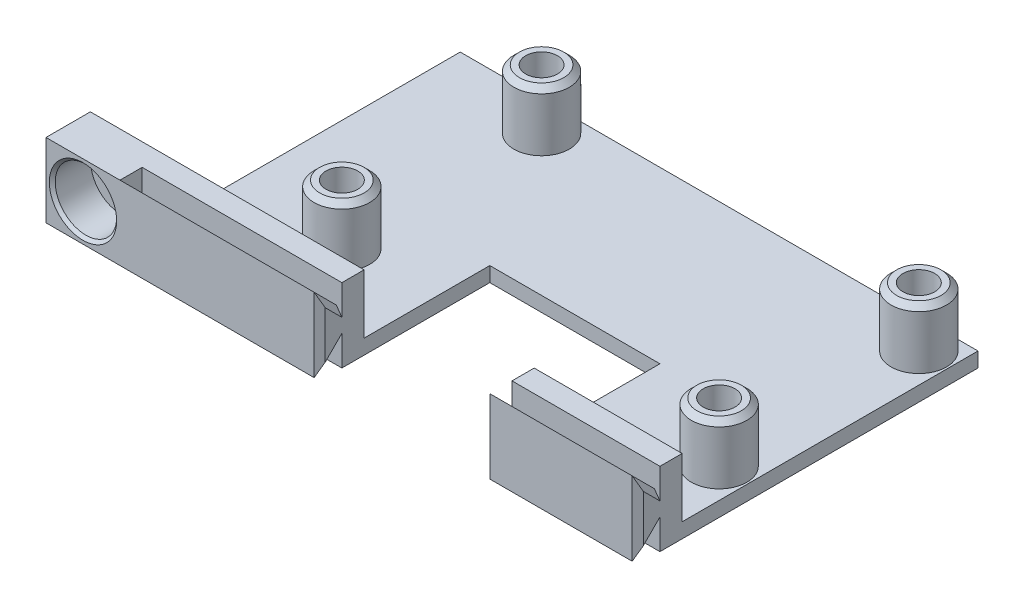
SolidWorks part; units mm, degrees
ref_plane "Front Plane" through (0, 0, 0) normal (0, 0, 1) x (1, 0, 0)
ref_plane "Top Plane" through (0, 0, 0) normal (0, 1, 0) x (1, 0, 0)
ref_plane "Right Plane" through (0, 0, 0) normal (1, 0, 0) x (0, 0, -1)
sketch "Sketch1" plane through (0, 0, 0) normal (0, 1, 0) x (1, 0, 0)
  line L1 (0, 0) -> (70, 0)
  line L2 (0, 0) -> (0, 35)
  line L3 (0, 35) -> (70, 35)
  line L4 (70, 0) -> (70, 35)
  dimension "D1" = 35
  dimension "D2" = 70
extrude "Boss-Extrude1" add sketch "Sketch1" along normal blind 2
sketch "Sketch2" plane through (0, 2, 0) normal (0, 1, 0) x (1, 0, 0)
  line L0 (70, 35) -> (0, 35) construction
  line L1 (70, 0) -> (70, 35) construction
  circle A0 centre (66, 31) radius 3.75
  circle A1 centre (15, 31) radius 3.75
  circle A2 centre (15, 4) radius 3.75
  circle A3 centre (66, 4) radius 3.75
  dimension "D1" = 2
  dimension "D3" = 51
  dimension "D4" = 27
  dimension "D5" = 4
  dimension "D6" = 4
  dimension "D7" = 7.5
  dimension "D2" = 2
extrude "Boss-Extrude2" add sketch "Sketch2" along normal blind 8
sketch "Sketch6" plane through (0, 0, 0) normal (0, 0, 1) x (1, 0, 0)
  line L4 (0, 0) -> (70, 0)
  line L5 (70, 0) -> (70, 2)
  line L6 (70, 2) -> (0, 2)
  line L7 (0, 2) -> (0, 0)
  line L8 (0, 0) -> (70, 0)
  line L9 (70, 0) -> (70, 2)
  line L10 (70, 2) -> (0, 2)
  line L11 (0, 2) -> (0, 0)
  dimension "D1" = 0
extrude "Boss-Extrude3" add sketch "Sketch6" along normal blind 2
hole_wizard "Ø4.3 (4.3) Diameter Hole1" positions "Sketch3" profile "Sketch4" hole size "Ø4.3" standard "DIN" end condition through all
sketch "Sketch3" plane through (0, 10, 0) normal (0, 1, 0) x (1, 0, 0)
  point P0 (66, 31)
  point P3 (15, 31)
  point P6 (15, 4)
  point P9 (66, 4)
sketch "Sketch4" plane through (66, 10, -31) normal (1, 0, 0) x (0, 0, 1)
  line L0 (0, 0) -> (0, 10)
  line L1 (0, 10) -> (2.15, 10)
  line L2 (2.15, 10) -> (2.15, 0)
  line L5 (2.15, 0) -> (0, 0)
  line L11 (0, -6.35) -> (0, 107.95) construction
  dimension "Thru Hole Dia." = 4.3
  dimension "Thru Hole Depth" = 10
chamfer "Chamfer1" distance 0.75 angle 45 4 edges at (15, 10, -0.25) (66, 10, -0.25) (66, 10, -27.25) (15, 10, -27.25)
sketch "Sketch5" plane through (0, 0, 0) normal (0, -1, 0) x (1, 0, 0)
  line L1 (27, -12) -> (50, -12)
  line L2 (27, -12) -> (27, 2)
  line L3 (27, 2) -> (50, 2)
  line L4 (50, -12) -> (50, 2)
  line L5 (27, -4) -> (15, -4) construction
  line L6 (50, -4) -> (66, -4) construction
  line L8 (0, 2) -> (70, 2) construction
  circle A4 centre (15, -4) radius 2.15 construction
  circle A5 centre (66, -4) radius 2.15 construction
  dimension "D1" = 14
  dimension "D2" = 12
  dimension "D3" = 16
extrude "Cut-Extrude1" cut sketch "Sketch5" against normal through all
fillet "Fillet1" [suppressed] radius 3
chamfer "Chamfer2" [suppressed] distance 2 angle 45
sketch "Sketch7" plane through (0, 0, 2) normal (0, 0, 1) x (1, 0, 0)
  line L0 (27, 0) -> (27, 2) construction
  line L1 (27, 2) -> (0, 2) construction
  line L2 (0, 2) -> (0, 0) construction
  line L3 (0, 0) -> (27, 0) construction
  line L4 (50, 2) -> (50, 0) construction
  line L5 (50, 0) -> (70, 0) construction
  line L6 (70, 0) -> (70, 2) construction
  line L7 (70, 2) -> (50, 2) construction
  line L8 (27, 0) -> (27, 2)
  line L9 (27, 2) -> (0, 2)
  line L10 (0, 2) -> (0, 0)
  line L11 (0, 0) -> (27, 0)
  line L12 (50, 2) -> (50, 0)
  line L13 (50, 0) -> (70, 0)
  line L14 (70, 0) -> (70, 2)
  line L15 (70, 2) -> (50, 2)
extrude "Boss-Extrude4" add sketch "Sketch7" along normal blind 3
sketch "Sketch9" plane through (0, 0, 5) normal (0, 0, 1) x (1, 0, 0)
  line L0 (70, 0) -> (70, 2) construction
  line L1 (0, 0) -> (27, 0)
  line L2 (0, 0) -> (0, 10)
  line L3 (0, 10) -> (27, 10)
  line L4 (27, 0) -> (27, 10)
  line L5 (50, 0) -> (70, 0)
  line L6 (50, 0) -> (50, 10)
  line L7 (50, 10) -> (70, 10)
  line L8 (70, 0) -> (70, 10)
  line L9 (27, 2) -> (27, 0) construction
  line L10 (18, 10) -> (12, 10) construction
extrude "Boss-Extrude5" add sketch "Sketch9" along normal blind 3
sketch "Sketch10" plane through (70, 0, 0) normal (1, 0, 0) x (0, 0, -1)
  line L0 (-8, 7) -> (-11, 10)
  line L1 (-8, 0) -> (-8, 10) construction
  line L2 (-11, 10) -> (-11, 0)
  line L3 (-11, 0) -> (-8, 3)
  line L4 (-8, 3) -> (-8, 7)
  line L5 (-8, 10) -> (-8, 7) construction
  line L6 (-8, 3) -> (-8, 0) construction
  line L7 (-8, 10) -> (-11, 10) construction
  line L8 (-8, 0) -> (-11, 0) construction
  dimension "D3" = 3
extrude "Boss-Extrude6" add sketch "Sketch10" against normal up to surface (20 mm away) up to face at (50, 4, 0.3333)
extrude "Boss-Extrude7" add sketch "Sketch10<2>" against normal up to surface (70 mm away) from surface up to face at (0, 4, -7.3333) starting at face at (27, 4, 0.3333)
sketch "Sketch10<2>" plane through (70, 0, 0) normal (1, 0, 0) x (0, 0, -1) same geometry as "Sketch10"
chamfer "Chamfer3" distance 0.75 angle 45 6 edges at (70, 8.5, 9.5) (70, 5, 11) (70, 1.5, 9.5) (27, 8.5, 9.5) (27, 5, 11) (27, 1.5, 9.5)
sketch "Sketch11" plane through (0, 0, 0) normal (-1, 0, 0) x (0, 0, 1)
  line L1 (5, 10) -> (11, 10)
  line L2 (5, 10) -> (5, 0)
  line L3 (5, 0) -> (11, 0)
  line L4 (11, 10) -> (11, 0)
extrude "Boss-Extrude8" add sketch "Sketch11" along normal blind 10
sketch "Sketch12" plane through (0, 0, 11) normal (0, 0, 1) x (1, 0, 0)
  line L0 (-10, 0) -> (0, 0) construction
  line L1 (-10, 10) -> (0, 10) construction
  line L2 (-10, 10) -> (-10, 0) construction
  line L3 (-10, 0) -> (0, 0) construction
  line L4 (0, 10) -> (0, 0) construction
  line L5 (0, 0) -> (-10, 10) construction
  line L6 (-10, 0) -> (0, 10) construction
  circle A0 centre (-5, 5) radius 4.15
  dimension "D1" = 8.3
extrude "Cut-Extrude2" cut sketch "Sketch12" against normal blind 5.2
chamfer "Chamfer4" distance 0.4 angle 45 1 edges at (-0.85, 5, 11)
